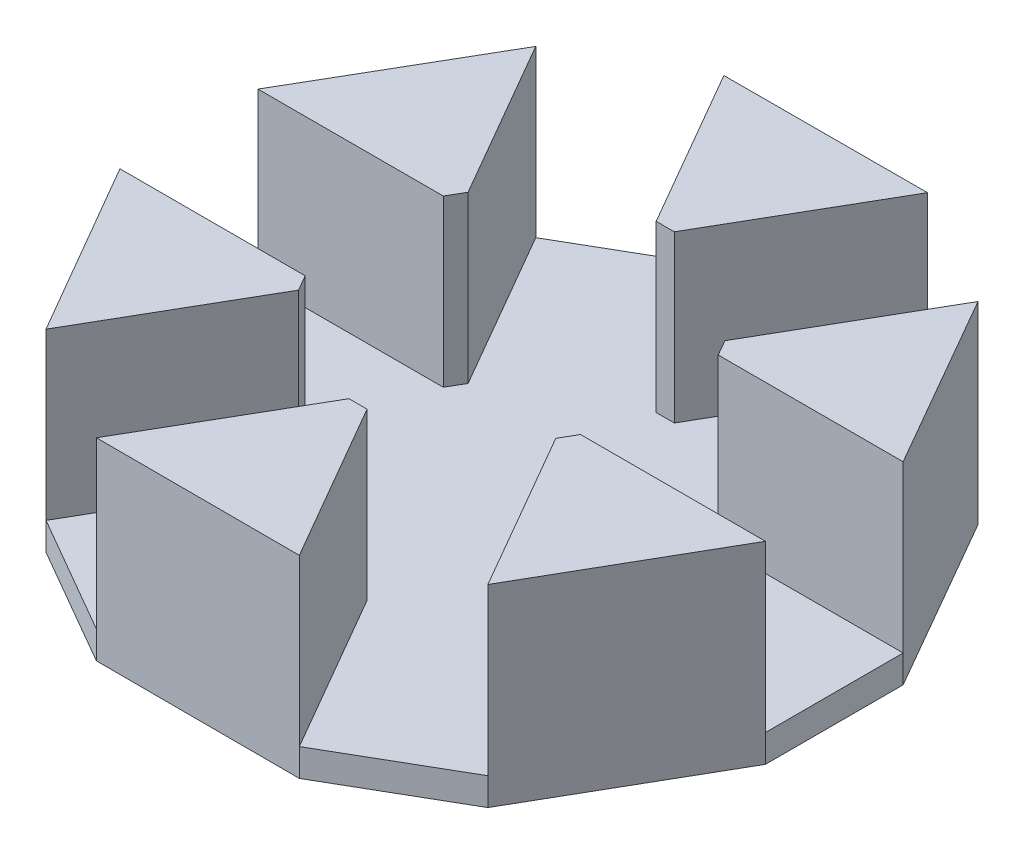
SolidWorks part; units mm, degrees
ref_plane "Front Plane" through (0, 0, 0) normal (0, 0, 1) x (1, 0, 0)
ref_plane "Top Plane" through (0, 0, 0) normal (0, 1, 0) x (1, 0, 0)
ref_plane "Right Plane" through (0, 0, 0) normal (1, 0, 0) x (0, 0, -1)
sketch "Sketch1" plane through (0, 0, 0) normal (0, 1, 0) x (1, 0, 0)
  line L2 (452.6998, -164.3415) -> (463.5011, -170.5776)
  line L7 (452.6998, -119.983) -> (463.5014, -113.7465)
  line L44 (461.0736, -134.4867) -> (452.6998, -119.983)
  line L78 (443.468, -135.9122) -> (452.6998, -119.983)
  line L79 (460.2505, -135.9064) -> (443.468, -135.9122)
  line L84 (461.0736, -134.4867) -> (460.2505, -135.9064)
  line L86 (471.8756, -128.25) -> (463.5014, -113.7465)
  line L87 (481.9124, -113.7155) -> (463.5014, -113.7465)
  line L88 (473.5166, -128.247) -> (481.9124, -113.7155)
  line L89 (471.8756, -128.25) -> (473.5166, -128.247)
  line L90 (461.0736, -149.8377) -> (452.6998, -164.3415)
  line L91 (443.468, -148.4123) -> (452.6998, -164.3415)
  line L92 (460.2505, -148.418) -> (443.468, -148.4123)
  line L93 (461.0736, -149.8377) -> (460.2505, -148.418)
  line L94 (471.8748, -156.0738) -> (473.5158, -156.0767)
  line L106 (473.5158, -156.0767) -> (481.9121, -170.608)
  line L123 (481.9121, -170.608) -> (463.5011, -170.5776)
  line L124 (471.8748, -156.0738) -> (463.5011, -170.5776)
  line L137 (485.1691, -148.3983) -> (501.9166, -148.3983)
  line L138 (492.7375, -164.3579) -> (501.9166, -148.3983)
  line L139 (484.3512, -149.8209) -> (492.7375, -164.3579)
  line L143 (485.1691, -148.3983) -> (484.3512, -149.8209)
  line L144 (485.1693, -135.9251) -> (484.3513, -134.5024)
  line L146 (484.3513, -134.5024) -> (492.738, -119.9657)
  line L147 (492.738, -119.9657) -> (501.9168, -135.9255)
  line L149 (485.1693, -135.9251) -> (501.9168, -135.9255)
  line L162 (481.9124, -113.7155) -> (492.738, -119.9657)
  line L163 (501.9168, -135.9255) -> (501.9166, -148.3983)
  line L164 (492.7375, -164.3579) -> (481.9121, -170.608)
  line L166 (443.468, -148.4123) -> (443.468, -135.9122)
extrude "Boss-Extrude1" add sketch "Sketch1" against normal blind 2.5 contours L90 L93 L92 L91 | L166 L92 L93 L90 L2 L124 L94 L106 L164 L139 L143 L137 L163 L149 L144 L146 L162 L88 L89 L86 L7 L44 L84 L79 | L84 L44 L78 L79 | L94 L124 L123 L106 | L137 L143 L139 L138 | L144 L149 L147 L146 | L86 L89 L88 L87 region at (472.706, 0, 142.1619) region at (452.6198, 0, 153.7628) region at (472.7025, 0, 165.3576) region at (452.6198, 0, 130.5617) region at (492.7953, 0, 153.757) region at (472.703, 0, 118.9662) region at (492.7956, 0, 130.5666)
extrude "Boss-Extrude2" add sketch "Sketch1<12>" along normal blind 15 contours L94 L124 L123 L106 | L90 L93 L92 L91 | L84 L44 L78 L79 | L86 L89 L88 L87 | L144 L149 L147 L146 | L137 L143 L139 L138 region at (452.6198, 0, 153.7628) region at (472.7025, 0, 165.3576) region at (452.6198, 0, 130.5617) region at (492.7953, 0, 153.757) region at (472.703, 0, 118.9662) region at (492.7956, 0, 130.5666)
sketch "Sketch1<12>" plane through (0, 0, 0) normal (0, 1, 0) x (1, 0, 0) same geometry as "Sketch1"
